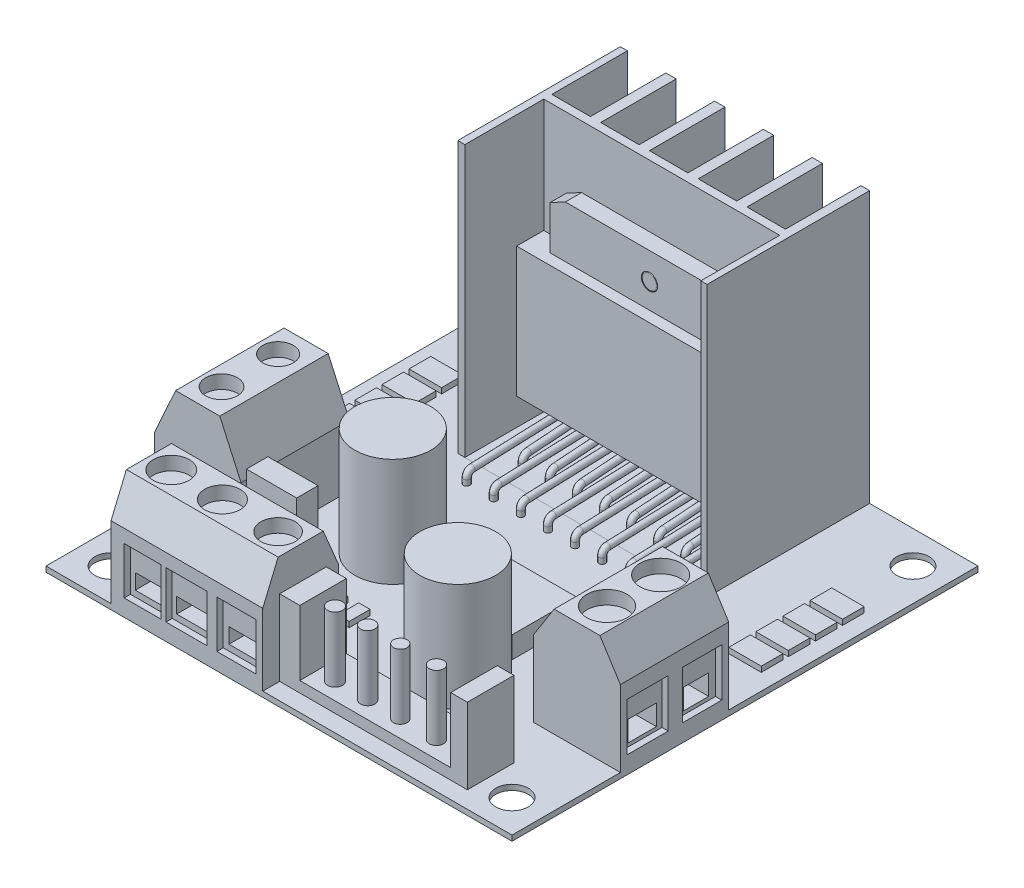
SolidWorks part; units mm, degrees
ref_plane "Front Plane" through (0, 0, 0) normal (0, 0, 1) x (1, 0, 0)
ref_plane "Top Plane" through (0, 0, 0) normal (0, 1, 0) x (1, 0, 0)
ref_plane "Right Plane" through (0, 0, 0) normal (1, 0, 0) x (0, 0, -1)
sketch "Sketch1" plane through (0, 0, 0) normal (0, 1, 0) x (1, 0, 0)
  line L0 (-19.7197, 23.0557) -> (-16.7197, 23.0557)
  line L1 (21.7803, 32.0557) -> (-21.2197, 32.0557)
  line L2 (21.7803, 32.0557) -> (21.7803, -10.9443)
  line L3 (21.7803, -10.9443) -> (-21.2197, -10.9443)
  line L4 (-21.2197, 32.0557) -> (-21.2197, -10.9443)
  line L5 (11.7803, 17.0557) -> (-11.2197, 17.0557)
  line L6 (11.7803, 17.0557) -> (11.7803, 32.0557)
  line L7 (11.7803, 32.0557) -> (-11.2197, 32.0557)
  line L8 (-11.2197, 17.0557) -> (-11.2197, 32.0557)
  line L9 (17.2803, 23.0557) -> (20.2803, 23.0557)
  line L10 (17.2803, 23.0557) -> (17.2803, 21.0557)
  line L11 (17.2803, 21.0557) -> (20.2803, 21.0557)
  line L12 (20.2803, 23.0557) -> (20.2803, 21.0557)
  line L13 (17.2803, 23.0557) -> (20.2803, 21.0557) construction
  line L14 (17.2803, 21.0557) -> (20.2803, 23.0557) construction
  line L15 (-16.7197, 23.0557) -> (-16.7197, 21.0557)
  line L16 (-19.7197, 21.0557) -> (-16.7197, 21.0557)
  line L17 (-19.7197, 23.0557) -> (-19.7197, 21.0557)
  line L18 (-19.7197, 20.5557) -> (-16.7197, 20.5557)
  line L19 (-16.7197, 20.5557) -> (-16.7197, 18.5557)
  line L20 (-19.7197, 18.5557) -> (-16.7197, 18.5557)
  line L21 (-19.7197, 20.5557) -> (-19.7197, 18.5557)
  line L22 (-19.7197, 18.0557) -> (-16.7197, 18.0557)
  line L23 (-16.7197, 18.0557) -> (-16.7197, 16.0557)
  line L24 (-19.7197, 16.0557) -> (-16.7197, 16.0557)
  line L25 (-19.7197, 18.0557) -> (-19.7197, 16.0557)
  line L26 (-19.7197, 15.5557) -> (-16.7197, 15.5557)
  line L27 (-16.7197, 15.5557) -> (-16.7197, 13.5557)
  line L28 (-19.7197, 13.5557) -> (-16.7197, 13.5557)
  line L29 (-19.7197, 15.5557) -> (-19.7197, 13.5557)
  line L30 (17.2803, 20.5557) -> (20.2803, 20.5557)
  line L31 (20.2803, 20.5557) -> (20.2803, 18.5557)
  line L32 (17.2803, 18.5557) -> (20.2803, 18.5557)
  line L33 (17.2803, 20.5557) -> (17.2803, 18.5557)
  line L34 (17.2803, 18.0557) -> (20.2803, 18.0557)
  line L35 (20.2803, 18.0557) -> (20.2803, 16.0557)
  line L36 (17.2803, 16.0557) -> (20.2803, 16.0557)
  line L37 (17.2803, 18.0557) -> (17.2803, 16.0557)
  line L38 (17.2803, 15.5557) -> (20.2803, 15.5557)
  line L39 (20.2803, 15.5557) -> (20.2803, 13.5557)
  line L40 (17.2803, 13.5557) -> (20.2803, 13.5557)
  line L41 (17.2803, 15.5557) -> (17.2803, 13.5557)
  line L42 (-13.2197, 9.0557) -> (-13.2197, -0.9443)
  line L43 (21.7803, 9.0557) -> (13.7803, 9.0557)
  line L44 (21.7803, 9.0557) -> (21.7803, -0.9443)
  line L45 (21.7803, -0.9443) -> (13.7803, -0.9443)
  line L46 (13.7803, 9.0557) -> (13.7803, -0.9443)
  line L47 (-13.2197, 9.0557) -> (-21.2197, 9.0557)
  line L48 (-13.2197, -0.9443) -> (-21.2197, -0.9443)
  line L49 (-21.2197, 9.0557) -> (-21.2197, -0.9443)
  line L51 (-1.2197, -10.9443) -> (-15.2197, -10.9443)
  line L52 (-1.2197, -10.9443) -> (-1.2197, -3.9443)
  line L53 (-1.2197, -3.9443) -> (-15.2197, -3.9443)
  line L54 (-15.2197, -10.9443) -> (-15.2197, -3.9443)
  line L55 (1.7803, 9.0557) -> (7.7803, 9.0557)
  line L56 (1.7803, 9.0557) -> (1.7803, 3.0557)
  line L57 (1.7803, 3.0557) -> (7.7803, 3.0557)
  line L58 (7.7803, 9.0557) -> (7.7803, 3.0557)
  line L59 (-12.7199, 1.0312) -> (-8.0906, 1.0312)
  line L60 (-12.7199, 1.0312) -> (-12.7199, -0.9443)
  line L61 (-12.7199, -0.9443) -> (-8.0906, -0.9443)
  line L62 (-8.0906, 1.0312) -> (-8.0906, -0.9443)
  line L63 (-6.2197, 0.0434) -> (-4.343, 0.0434)
  line L64 (-6.2197, 0.0434) -> (-6.2197, -0.9443)
  line L65 (-6.2197, -0.9443) -> (-4.343, -0.9443)
  line L66 (-4.343, 0.0434) -> (-4.343, -0.9443)
  line L67 (-2.3039, 0.0434) -> (-3.351, 0.0434)
  line L68 (-2.3039, 0.0434) -> (-2.3039, -1.8897)
  line L69 (-2.3039, -1.8897) -> (-3.351, -1.8897)
  line L70 (-3.351, 0.0434) -> (-3.351, -1.8897)
  line L71 (-1.2197, -5.0862) -> (16.1034, -5.0862)
  line L72 (-1.2197, -5.0862) -> (-1.2197, -9.3849)
  line L73 (-1.2197, -9.3849) -> (16.1034, -9.3849)
  line L74 (16.1034, -5.0862) -> (16.1034, -9.3849)
  circle A0 centre (18.7803, 29.0557) radius 1.5
  circle A1 centre (-18.2197, 29.0557) radius 1.5
  circle A2 centre (-18.2197, -7.9443) radius 1.5
  circle A3 centre (18.7803, -7.9443) radius 1.5
  circle A4 centre (-6.2197, 6.0557) radius 3.5
  circle A5 centre (6.7803, -0.9443) radius 3.5
  point P0 (0, 0)
  point P8 (18.7803, 22.0557)
  point P25 (-18.2197, 22.0557)
  point P30 (-18.2197, 19.5557)
  point P35 (-18.2197, 17.0557)
  point P40 (-18.2197, 14.5557)
  point P45 (18.7803, 19.5557)
  point P50 (18.7803, 17.0557)
  point P55 (18.7803, 14.5557)
  point P62 (17.7803, 9.0557)
  point P75 (-1.2197, -7.4443)
  dimension "D3" = 3
  dimension "D9" = 3
  dimension "D20" = 7
  dimension "D21" = 7
  dimension "D1" = 43
  dimension "D2" = 43
  dimension "D4" = 3
  dimension "D5" = 2
  dimension "D6" = 23
  dimension "D7" = 15
  dimension "D10" = 10
  dimension "D11" = 2
  dimension "D12" = 3
  dimension "D14" = 20
  dimension "D15" = 10
  dimension "D16" = 8
  dimension "D18" = 17
  dimension "D19" = 15
  dimension "D22" = 10
  dimension "D23" = 15
  dimension "D24" = 20
  dimension "D25" = 6
  dimension "D26" = 7
  dimension "D27" = 20
  dimension "D28" = 6
  dimension "D29" = 6
  dimension "D30" = 20
  dimension "D8" = 2
  dimension "D13" = 2
  dimension "D17" = 2
extrude "Boss-Extrude1" add sketch "Sketch1" against normal blind 0.5 contours L71 L74 L73 L52 L3 L2 L45 L46 L43 L1 L6 L5 L8 L4 L47 L42 L48 L54 L53 A5 A4 A3 A2 A1 A0 L70 L67 L68 L69 L41 L38 L39 L40 L37 L34 L35 L36 region at (0.5403, 0, -10.3951)
ref_plane "Plane1" through (-11.2197, 0, -32.0557) normal (0, 0, -1) x (-1, 0, 0)
extrude "Boss-Extrude2" add sketch "Sketch1<3>" along normal blind 25 and the other way blind 0.5 separate body contours L8 L5 L6 L1 region at (0.2803, 0, -24.5557)
sketch "Sketch1<3>" plane through (0, 0, 0) normal (0, 1, 0) x (1, 0, 0) same geometry as "Sketch1"
extrude "Boss-Extrude3" add sketch "Sketch1<4>" along normal blind 0.5 and the other way blind 0.5 separate body contours L12 L9 L10 L11 | L30 L33 L32 L31 | L34 L37 L36 L35 | L38 L41 L40 L39 | L0 L17 L16 L15 | L18 L21 L20 L19 | L22 L25 L24 L23 | L26 L29 L28 L27 | L66 L63 L64 L65 | L67 L70 L69 L68 region at (-18.2197, 0, -22.0557) region at (18.7803, 0, -22.0557) region at (-18.2197, 0, -19.5557) region at (-18.2197, 0, -17.0557) region at (-18.2197, 0, -14.5557) region at (18.7803, 0, -19.5557) region at (18.7803, 0, -17.0557) region at (18.7803, 0, -14.5557) region at (-5.2814, 0, 0.4505) region at (-2.8274, 0, 0.9232)
sketch "Sketch1<4>" plane through (0, 0, 0) normal (0, 1, 0) x (1, 0, 0) same geometry as "Sketch1"
extrude "Boss-Extrude4" add sketch "Sketch1<5>" along normal blind 10 and the other way blind 0.5 contours A4 | A5 region at (-6.2197, 0, -6.0557) region at (6.7803, 0, 0.9443)
sketch "Sketch1<5>" plane through (0, 0, 0) normal (0, 1, 0) x (1, 0, 0) same geometry as "Sketch1"
extrude "Boss-Extrude5" add sketch "Sketch1<6>" along normal blind 2 separate body contours L58 L55 L56 L57 region at (4.7803, 0, -6.0557)
sketch "Sketch1<6>" plane through (0, 0, 0) normal (0, 1, 0) x (1, 0, 0) same geometry as "Sketch1"
extrude "Boss-Extrude6" add sketch "Sketch1<7>" along normal blind 10 and the other way blind 0.5 contours L48 L42 L47 L4 | L43 L46 L45 L2 | L54 L3 L52 L53 region at (17.7803, 0, -4.0557) region at (-17.2197, 0, -4.0557) region at (-8.2197, 0, 7.4443)
sketch "Sketch1<7>" plane through (0, 0, 0) normal (0, 1, 0) x (1, 0, 0) same geometry as "Sketch1"
extrude "Boss-Extrude7" add sketch "Sketch1<8>" along normal blind 7 and the other way blind 0.5 contours L62 L59 L60 L61 | L74 L71 L52 L73 region at (7.4418, 0, 7.2355) region at (-10.4053, 0, -0.0434)
sketch "Sketch1<8>" plane through (0, 0, 0) normal (0, 1, 0) x (1, 0, 0) same geometry as "Sketch1"
ref_plane "Plane2" through (0, 25, 0) normal (0, 1, 0) x (1, 0, 0)
sketch "Sketch3" plane through (0, 25, 0) normal (0, 1, 0) x (1, 0, 0)
  line L0 (11.7803, 17.0557) -> (-11.2197, 17.0557) construction
  line L1 (-10.5697, 17.0557) -> (11.2003, 17.0557)
  line L2 (-10.5697, 17.0557) -> (-10.5697, 24.3372)
  line L3 (-10.5697, 24.3372) -> (11.2003, 24.3372)
  line L4 (11.2003, 17.0557) -> (11.2003, 24.3372)
  line L5 (11.7803, 32.0557) -> (-11.2197, 32.0557) construction
  line L6 (-10.5697, 32.0557) -> (-7.0197, 32.0557)
  line L7 (-10.5697, 32.0557) -> (-10.5697, 25.0872)
  line L8 (-10.5697, 25.0872) -> (-7.0197, 25.0872)
  line L9 (-7.0197, 32.0557) -> (-7.0197, 25.0872)
  line L10 (-11.2197, 17.0557) -> (-11.2197, 32.0557) construction
  line L11 (11.7803, 17.0557) -> (11.7803, 32.0557) construction
  line L12 (-2.5197, 32.0557) -> (-2.5197, 25.0872)
  line L13 (-6.0697, 32.0557) -> (-2.5197, 32.0557)
  line L14 (-6.0697, 25.0872) -> (-2.5197, 25.0872)
  line L15 (-6.0697, 32.0557) -> (-6.0697, 25.0872)
  line L16 (1.9803, 32.0557) -> (1.9803, 25.0872)
  line L17 (-1.5697, 32.0557) -> (1.9803, 32.0557)
  line L18 (-1.5697, 25.0872) -> (1.9803, 25.0872)
  line L19 (-1.5697, 32.0557) -> (-1.5697, 25.0872)
  line L20 (6.4803, 32.0557) -> (6.4803, 25.0872)
  line L21 (2.9303, 32.0557) -> (6.4803, 32.0557)
  line L22 (2.9303, 25.0872) -> (6.4803, 25.0872)
  line L23 (2.9303, 32.0557) -> (2.9303, 25.0872)
  line L24 (10.9803, 32.0557) -> (10.9803, 25.0872)
  line L25 (7.4303, 32.0557) -> (10.9803, 32.0557)
  line L26 (7.4303, 25.0872) -> (10.9803, 25.0872)
  line L27 (7.4303, 32.0557) -> (7.4303, 25.0872)
  dimension "D1" = 3.55
  dimension "D2" = 0.65
  dimension "D3" = 0.65
  dimension "D4" = 0.75
  dimension "D5" = 0.58
  dimension "D6" = 5
extrude "Cut-Extrude1" cut sketch "Sketch3" against normal blind 25
ref_plane "Plane3" through (0, 0, -24.3372) normal (0, 0, 1) x (1, 0, 0)
sketch "Sketch4" plane through (0, 0, -24.3372) normal (0, 0, 1) x (1, 0, 0)
  line L0 (11.2003, 0) -> (11.2003, 25) construction
  line L1 (11.2003, 14.5) -> (-10.6219, 14.5)
  line L2 (11.2003, 14.5) -> (11.2003, 2.5)
  line L3 (11.2003, 2.5) -> (-10.6219, 2.5)
  line L4 (-10.6219, 14.5) -> (-10.6219, 2.5)
  line L5 (11.2003, -0.5) -> (-10.5697, -0.5) construction
  line L6 (9.6818, 18.5221) -> (8.4759, 19.2721)
  line L7 (9.6818, 14.5) -> (-8.4854, 14.5)
  line L8 (9.6818, 14.5) -> (9.6818, 18.5221)
  line L9 (9.6818, 18.5221) -> (-8.4854, 18.5221)
  line L10 (-8.4854, 14.5) -> (-8.4854, 18.5221)
  line L11 (8.4759, 18.5221) -> (-7.0807, 18.5221)
  line L12 (8.4759, 18.5221) -> (8.4759, 19.2721)
  line L13 (8.4759, 19.2721) -> (-7.0807, 19.2721)
  line L14 (-7.0807, 18.5221) -> (-7.0807, 19.2721)
  line L15 (8.4759, 19.2721) -> (7.963, 19.2843)
  line L16 (-7.0807, 19.2721) -> (-8.4854, 18.5221)
  circle A0 centre (0.6818, 16.7775) radius 0.75
  dimension "D1" = 12
  dimension "D2" = 15
  dimension "D4" = 0.75
extrude "Boss-Extrude8" add sketch "Sketch4" along normal blind 2.5 contours L1 L4 L3 L2 region at (0.2892, 8.5, -24.3372)
extrude "Boss-Extrude9" add sketch "Sketch4<4>" along normal blind 1.5 contours A0 region at (0.6818, 16.7775, -24.3372)
sketch "Sketch4<4>" plane through (0, 0, -24.3372) normal (0, 0, 1) x (1, 0, 0) same geometry as "Sketch4"
fillet "Fillet1" radius 0.1 1 edges at (1.4318, 16.7775, -22.8372)
sketch "Sketch5" plane through (0, 0, -24.3372) normal (0, 0, 1) x (1, 0, 0)
  circle A1 centre (-7.1466, 1.3112) radius 0.3
ref_plane "Plane4" through (0, 0, 0) normal (0, 1, 0) x (1, 0, 0)
sketch "Sketch6" plane through (0, 0, 0) normal (0, 1, 0) x (1, 0, 0)
  line L0 (-10.5697, 24.3372) -> (-10.5697, 17.0557) construction
  line L2 (11.7803, 17.0557) -> (-11.2197, 17.0557) construction
  circle A0 centre (-8.3997, 15.0557) radius 0.3
  point P7 (0.2803, 17.0557)
  dimension "D1" = 2.17
  dimension "D2" = 2
ref_plane "Plane5" through (-8.3997, 0, 0) normal (1, 0, 0) x (0, 0, -1)
sketch "Sketch7" plane through (-8.3997, 0, 0) normal (1, 0, 0) x (0, 0, -1)
  line L0 (15.0557, 0) -> (15.0557, 0.5014)
  line L1 (15.5372, 1.0011) -> (24.3456, 1.327)
  arc A0 (15.5372, 1.0011) -> (15.0557, 0.5014) centre (15.5557, 0.5014) ccw
  dimension "D1" = 0.5
sweep "Sweep8" add profiles "Sketch6" path "Sketch7"
pattern_linear "LPattern1" count 8 spacing 2.5 along (1, 0, 0) of "Sweep8"
ref_plane "Plane6" through (-7.1497, 0, 0) normal (1, 0, 0) x (0, 0, -1)
sketch "Sketch8" plane through (-7.1497, 0, 0) normal (1, 0, 0) x (0, 0, -1)
  line L0 (19.0004, 0) -> (19.0004, 0.4329)
  line L1 (19.4648, 0.9316) -> (24.3953, 1.2835)
  arc A0 (19.0004, 0.4329) -> (19.4648, 0.9316) centre (19.5004, 0.4329) cw
  dimension "D1" = 0.5
sweep "Sweep9" add profiles "Sketch5" path "Sketch8"
extrude "Boss-Extrude10" add sketch "Sketch4<5>" along normal blind 1.5 contours L10 L1 L8 L9 A0 | L14 L9 L12 L13 | L14 L16 L9 | L12 L9 L6 region at (0.5982, 14.6861, -24.3372) region at (8.8779, 18.7721, -24.3372) region at (-7.549, 18.7721, -24.3372) region at (0.6976, 18.8971, -24.3372)
sketch "Sketch4<5>" plane through (0, 0, -24.3372) normal (0, 0, 1) x (1, 0, 0) same geometry as "Sketch4"
pattern_linear "LPattern3" count 8 spacing 2.5 along (1, 0, 0) of "Sweep9"
ref_plane "Plane7" through (-15.2197, 0, 0) normal (-1, 0, 0) x (0, 0, 1)
sketch "Sketch10" plane through (-15.2197, 0, 0) normal (-1, 0, 0) x (0, 0, 1)
  line L0 (5.3649, 10) -> (3.9443, 6.6215)
  line L1 (10.9443, 10) -> (3.9443, 10) construction
  line L2 (3.9443, 0) -> (3.9443, 10) construction
  line L3 (7.4443, 10) -> (7.4443, 6.6215) construction
  line L4 (9.5238, 10) -> (10.9443, 6.6215)
  line L5 (5.3649, 10) -> (3.9443, 10)
  line L6 (3.9443, 10) -> (3.9443, 6.6215)
  line L7 (9.5238, 10) -> (10.9443, 10)
  line L8 (10.9443, 10) -> (10.9443, 6.6215)
extrude "Cut-Extrude2" cut sketch "Sketch10" against normal up to vertex (14 mm away) up to point (-1.2197, 10, 10.9443)
ref_plane "Plane8" through (0, 0, 0.9443) normal (0, 0, 1) x (1, 0, 0)
sketch "Sketch12" plane through (0, 0, 0.9443) normal (0, 0, 1) x (1, 0, 0)
  line L0 (-21.2197, 5.6537) -> (-19.2576, 10)
  line L1 (-21.2197, 0) -> (-21.2197, 10) construction
  line L2 (-13.2197, 10) -> (-21.2197, 10) construction
  line L3 (-19.2576, 10) -> (-21.2197, 10)
  line L4 (-21.2197, 10) -> (-21.2197, 5.6537)
  line L5 (-17.2197, 10) -> (-17.2197, 5.6537) construction
  line L6 (-13.2197, 10) -> (-13.2197, 5.6537)
  line L7 (-15.1819, 10) -> (-13.2197, 10)
  line L8 (-13.2197, 5.6537) -> (-15.1819, 10)
extrude "Cut-Extrude3" cut sketch "Sketch12" against normal blind 10
ref_plane "Plane9" through (0, 0, 0.9443) normal (0, 0, 1) x (1, 0, 0)
sketch "Sketch13" plane through (0, 0, 0.9443) normal (0, 0, 1) x (1, 0, 0)
  line L0 (19.8906, 10) -> (21.7803, 7.0236)
  line L1 (21.7803, 10) -> (13.7803, 10) construction
  line L2 (21.7803, 0) -> (21.7803, 10) construction
  line L3 (21.7803, 7.0236) -> (21.7803, 10)
  line L4 (21.7803, 10) -> (19.8906, 10)
  line L5 (17.7803, 10) -> (17.7803, 7.1326) construction
  line L6 (13.7803, 10) -> (15.6699, 10)
  line L7 (13.7803, 7.0236) -> (13.7803, 10)
  line L8 (15.6699, 10) -> (13.7803, 7.0236)
extrude "Cut-Extrude4" cut sketch "Sketch13" against normal blind 10
ref_plane "Plane10" through (0, 0, 14.3643) normal (0, 0, 1) x (1, 0, 0)
sketch "Sketch14" plane through (0, 0, 14.3643) normal (0, 0, 1) x (1, 0, 0)
  line L1 (-14.0071, 5.4095) -> (-10.5874, 5.4095)
  line L2 (-14.0071, 5.4095) -> (-14.0071, 1.0561)
  line L3 (-14.0071, 1.0561) -> (-10.5874, 1.0561)
  line L4 (-10.5874, 5.4095) -> (-10.5874, 1.0561)
  line L5 (-10.1506, 5.4095) -> (-6.3753, 5.4095)
  line L6 (-10.1506, 5.4095) -> (-10.1506, 1.0561)
  line L7 (-10.1506, 1.0561) -> (-6.3753, 1.0561)
  line L8 (-6.3753, 5.4095) -> (-6.3753, 1.0561)
  line L9 (-5.4476, 5.4095) -> (-1.8606, 5.4095)
  line L10 (-5.4476, 5.4095) -> (-5.4476, 1.0561)
  line L11 (-5.4476, 1.0561) -> (-1.8606, 1.0561)
  line L12 (-1.8606, 5.4095) -> (-1.8606, 1.0561)
  line L13 (-13.56, 3.0214) -> (-10.9822, 3.0214)
  line L14 (-13.56, 3.0214) -> (-13.56, 1.6082)
  line L15 (-13.56, 1.6082) -> (-10.9822, 1.6082)
  line L16 (-10.9822, 3.0214) -> (-10.9822, 1.6082)
  line L17 (-9.7389, 3.0214) -> (-6.9069, 3.0214)
  line L18 (-9.7389, 3.0214) -> (-9.7389, 1.6082)
  line L19 (-9.7389, 1.6082) -> (-6.9069, 1.6082)
  line L20 (-6.9069, 3.0214) -> (-6.9069, 1.6082)
  line L21 (-4.9207, 3.0214) -> (-2.382, 3.0214)
  line L22 (-4.9207, 3.0214) -> (-4.9207, 1.6082)
  line L23 (-4.9207, 1.6082) -> (-2.382, 1.6082)
  line L24 (-2.382, 3.0214) -> (-2.382, 1.6082)
extrude "Cut-Extrude6" cut sketch "Sketch14" against normal blind 4 contours L16 L13 L14 L15 | L4 L1 L2 L3 L13 L16 L15 L14 | L8 L5 L6 L7 L17 L20 L19 L18 | L12 L9 L10 L11 L21 L24 L23 L22 | L24 L21 L22 L23 | L17 L20 L19 L18 region at (-12.3057, 3.5302, 14.3643) region at (-8.2437, 3.5283, 14.3643) region at (-3.6549, 3.5066, 14.3643) region at (-12.2711, 2.3148, 14.3643) region at (-3.6513, 2.3148, 14.3643)
extrude "Cut-Extrude7" cut sketch "Sketch14<4>" against normal blind 8 contours L16 L13 L14 L15 | L20 L17 L18 L19 | L24 L21 L22 L23 region at (-12.2711, 2.3148, 14.3643) region at (-8.3229, 2.3148, 14.3643) region at (-3.6513, 2.3148, 14.3643)
sketch "Sketch14<4>" plane through (0, 0, 14.3643) normal (0, 0, 1) x (1, 0, 0) same geometry as "Sketch14"
ref_plane "Plane11" through (-21.2197, 0, 0) normal (-1, 0, 0) x (0, 0, 1)
sketch "Sketch15" plane through (-21.2197, 0, 0) normal (-1, 0, 0) x (0, 0, 1)
  line L1 (-8.6077, 4.509) -> (-4.6095, 4.509)
  line L2 (-8.6077, 4.509) -> (-8.6077, 0.5107)
  line L3 (-8.6077, 0.5107) -> (-4.6095, 0.5107)
  line L4 (-4.6095, 4.509) -> (-4.6095, 0.5107)
  line L5 (-3.5356, 4.509) -> (0.2809, 4.509)
  line L6 (-3.5356, 4.509) -> (-3.5356, 0.5107)
  line L7 (-3.5356, 0.5107) -> (0.2809, 0.5107)
  line L8 (0.2809, 4.509) -> (0.2809, 0.5107)
  line L9 (-8.079, 2.5098) -> (-5.0556, 2.5098)
  line L10 (-8.079, 2.5098) -> (-8.079, 0.7586)
  line L11 (-8.079, 0.7586) -> (-5.0556, 0.7586)
  line L12 (-5.0556, 2.5098) -> (-5.0556, 0.7586)
  line L13 (-2.9739, 2.5098) -> (-0.1156, 2.5098)
  line L14 (-2.9739, 2.5098) -> (-2.9739, 0.7586)
  line L15 (-2.9739, 0.7586) -> (-0.1156, 0.7586)
  line L16 (-0.1156, 2.5098) -> (-0.1156, 0.7586)
extrude "Cut-Extrude8" cut sketch "Sketch15" against normal blind 1.5 contours L12 L9 L10 L11 | L16 L13 L14 L15 | L4 L1 L2 L3 L9 L12 L11 L10 | L8 L5 L6 L7 L13 L16 L15 L14 region at (-21.2197, 2.9435, -6.6291) region at (-21.2197, 2.9373, -1.6677) region at (-21.2197, 1.6342, -6.5673) region at (-21.2197, 1.6342, -1.5447)
extrude "Cut-Extrude9" cut sketch "Sketch15<3>" against normal blind 3 contours L12 L9 L10 L11 | L16 L13 L14 L15 region at (-21.2197, 1.6342, -6.5673) region at (-21.2197, 1.6342, -1.5447)
sketch "Sketch15<3>" plane through (-21.2197, 0, 0) normal (-1, 0, 0) x (0, 0, 1) same geometry as "Sketch15"
ref_plane "Plane12" through (25.2003, 0, 0) normal (1, 0, 0) x (0, 0, -1)
sketch "Sketch16" plane through (25.2003, 0, 0) normal (1, 0, 0) x (0, 0, -1)
  line L1 (-0.3258, 5.5362) -> (3.4706, 5.5362)
  line L2 (-0.3258, 5.5362) -> (-0.3258, 1.1027)
  line L3 (-0.3258, 1.1027) -> (3.4706, 1.1027)
  line L4 (3.4706, 5.5362) -> (3.4706, 1.1027)
  line L5 (4.7871, 5.5362) -> (8.4201, 5.5362)
  line L6 (4.7871, 5.5362) -> (4.7871, 1.1027)
  line L7 (4.7871, 1.1027) -> (8.4201, 1.1027)
  line L8 (8.4201, 5.5362) -> (8.4201, 1.1027)
  line L9 (0.3425, 3.3194) -> (2.9568, 3.3194)
  line L10 (0.3425, 3.3194) -> (0.3425, 1.4266)
  line L11 (0.3425, 1.4266) -> (2.9568, 1.4266)
  line L12 (2.9568, 3.3194) -> (2.9568, 1.4266)
  line L13 (5.4498, 3.3194) -> (7.785, 3.3194)
  line L14 (5.4498, 3.3194) -> (5.4498, 1.4266)
  line L15 (5.4498, 1.4266) -> (7.785, 1.4266)
  line L16 (7.785, 3.3194) -> (7.785, 1.4266)
extrude "Cut-Extrude10" cut sketch "Sketch16" against normal blind 4 contours L12 L9 L10 L11 | L16 L13 L14 L15 | L4 L1 L2 L3 L9 L12 L11 L10 | L8 L5 L6 L7 L13 L16 L15 L14 region at (25.2003, 3.7136, -1.5402) region at (25.2003, 3.6774, -6.5984) region at (25.2003, 2.373, -1.6497) region at (25.2003, 2.373, -6.6174)
extrude "Cut-Extrude11" cut sketch "Sketch16<3>" against normal blind 6 contours L12 L9 L10 L11 | L16 L13 L14 L15 region at (25.2003, 2.373, -1.6497) region at (25.2003, 2.373, -6.6174)
sketch "Sketch16<3>" plane through (25.2003, 0, 0) normal (1, 0, 0) x (0, 0, -1) same geometry as "Sketch16"
ref_plane "Plane13" through (0, 7, 0) normal (0, 1, 0) x (1, 0, 0)
sketch "Sketch17" plane through (0, 7, 0) normal (0, 1, 0) x (1, 0, 0)
  line L0 (-1.2197, -5.0862) -> (16.1034, -5.0862) construction
  line L1 (0.6369, -5.0862) -> (14.566, -5.0862)
  line L2 (0.6369, -5.0862) -> (0.6369, -9.5171)
  line L3 (0.6369, -9.5171) -> (14.566, -9.5171)
  line L4 (14.566, -5.0862) -> (14.566, -9.5171)
  circle A0 centre (2.3101, -7.8052) radius 0.692
  circle A1 centre (5.3215, -7.8052) radius 0.6644
  circle A2 centre (8.3341, -7.8052) radius 0.6285
  circle A3 centre (11.671, -7.8052) radius 0.6623
extrude "Cut-Extrude12" cut sketch "Sketch17" against normal blind 6
ref_plane "Plane14" through (0, 10, 0) normal (0, 1, 0) x (1, 0, 0)
sketch "Sketch18" plane through (0, 10, 0) normal (0, 1, 0) x (1, 0, 0)
  circle A0 centre (-13.1184, -7.49) radius 1.6579
  circle A1 centre (-8.3987, -7.49) radius 1.6354
  circle A2 centre (-3.2607, -7.49) radius 1.587
  circle A4 centre (-17.4472, 1.4786) radius 1.4606
  circle A5 centre (-17.4472, 6.6968) radius 1.4061
  circle A6 centre (17.8579, 6.6968) radius 1.896
  circle A7 centre (17.8579, 1.7435) radius 1.8664
extrude "Cut-Extrude13" cut sketch "Sketch18" against normal blind 1.25
